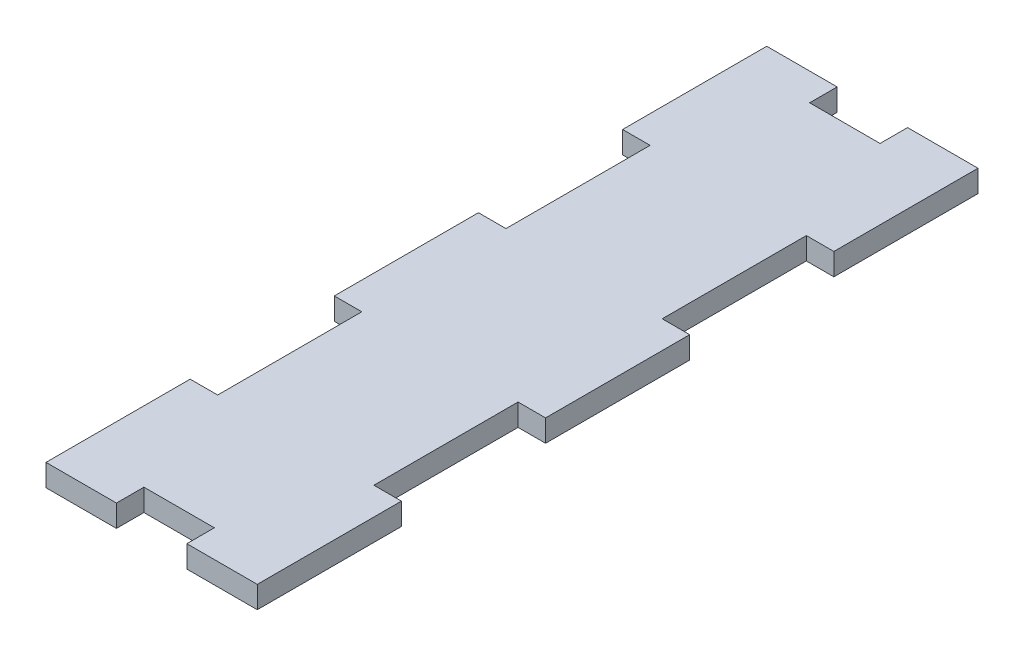
SolidWorks part; units mm, degrees
ref_plane "Front Plane" through (0, 0, 0) normal (0, 0, 1) x (1, 0, 0)
ref_plane "Top Plane" through (0, 0, 0) normal (0, 1, 0) x (1, 0, 0)
ref_plane "Right Plane" through (0, 0, 0) normal (1, 0, 0) x (0, 0, -1)
sketch "Sketch1" plane through (0, 0, 0) normal (0, 1, 0) x (1, 0, 0)
  line L1 (-12.192, -41.5925) -> (12.192, -41.5925)
  line L2 (-12.192, -41.5925) -> (-12.192, 41.5925)
  line L3 (-12.192, 41.5925) -> (12.192, 41.5925)
  line L4 (12.192, -41.5925) -> (12.192, 41.5925)
  line L5 (-12.192, -41.5925) -> (12.192, 41.5925) construction
  line L6 (-12.192, 41.5925) -> (12.192, -41.5925) construction
  point P0 (0, 0)
  dimension "D1" = 24.384
  dimension "D2" = 83.185
extrude "Boss-Extrude1" add sketch "Sketch1" along normal blind 2.54
sketch "Sketch2" plane through (0, 2.54, 0) normal (0, 1, 0) x (1, 0, 0)
  line L0 (-12.192, 41.5925) -> (-12.192, -41.5925) construction
  line L1 (12.192, -41.5925) -> (12.192, 41.5925) construction
  line L2 (-15.367, -8.3185) -> (-9.017, -8.3185) construction
  line L3 (-15.367, -8.3185) -> (-15.367, 8.3185) construction
  line L4 (-15.367, 8.3185) -> (-9.017, 8.3185) construction
  line L5 (-9.017, -8.3185) -> (-9.017, 8.3185) construction
  line L6 (-15.367, -8.3185) -> (-9.017, 8.3185) construction
  line L7 (-15.367, 8.3185) -> (-9.017, -8.3185) construction
  line L8 (-9.017, 8.3185) -> (-12.192, 8.3185)
  line L9 (-9.017, 8.3185) -> (-9.017, 24.9555)
  line L10 (-9.017, 24.9555) -> (-12.192, 24.9555)
  line L11 (-12.192, 8.3185) -> (-12.192, 24.9555)
  line L12 (12.192, 8.3185) -> (9.017, 8.3185)
  line L13 (12.192, 8.3185) -> (12.192, 24.9555)
  line L14 (12.192, 24.9555) -> (9.017, 24.9555)
  line L15 (9.017, 8.3185) -> (9.017, 24.9555)
  point P3 (-12.192, 0)
  dimension "D1" = 6.35
  dimension "D2" = 16.637
  dimension "D3" = 16.637
  dimension "D4" = 3.175
extrude "Cut-Extrude1" cut sketch "Sketch2" against normal blind 2.54
pattern_linear "LPattern1" count 2 spacing 33.274 along (0, 0, 1) of "Cut-Extrude1"
sketch "Sketch3" plane through (0, 2.54, 0) normal (0, 1, 0) x (1, 0, 0)
  line L0 (12.192, 41.5925) -> (-12.192, 41.5925) construction
  line L1 (-4.064, 38.4175) -> (4.064, 38.4175)
  line L2 (-4.064, 38.4175) -> (-4.064, 44.7675)
  line L3 (-4.064, 44.7675) -> (4.064, 44.7675)
  line L4 (4.064, 38.4175) -> (4.064, 44.7675)
  line L5 (-4.064, 38.4175) -> (4.064, 44.7675) construction
  line L6 (-4.064, 44.7675) -> (4.064, 38.4175) construction
  line L7 (-12.192, -41.5925) -> (12.192, -41.5925) construction
  line L8 (-4.064, -44.7675) -> (4.064, -44.7675)
  line L9 (-4.064, -44.7675) -> (-4.064, -38.4175)
  line L10 (-4.064, -38.4175) -> (4.064, -38.4175)
  line L11 (4.064, -44.7675) -> (4.064, -38.4175)
  line L12 (-4.064, -44.7675) -> (4.064, -38.4175) construction
  line L13 (-4.064, -38.4175) -> (4.064, -44.7675) construction
  point P0 (0, 41.5925)
  point P7 (0, -41.5925)
  dimension "D1" = 6.35
  dimension "D2" = 8.128
  dimension "D3" = 6.35
extrude "Cut-Extrude2" cut sketch "Sketch3" against normal blind 2.54
